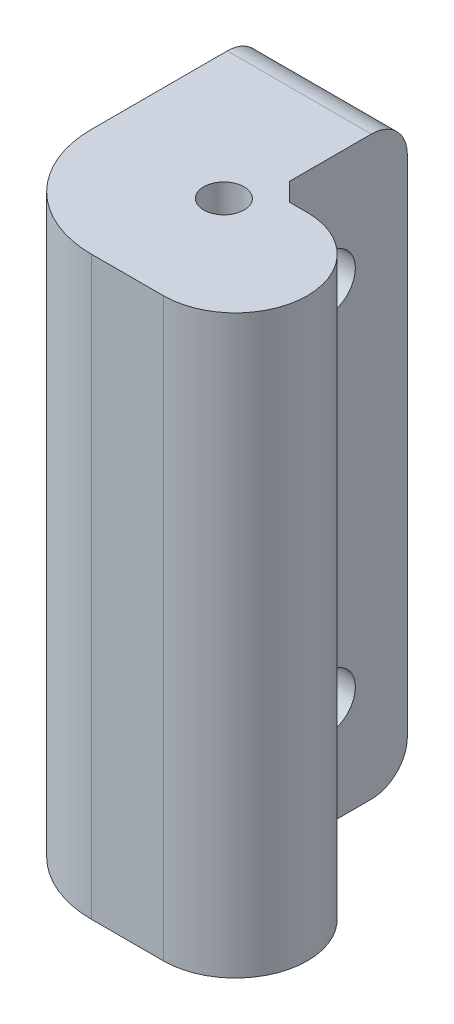
SolidWorks part; units mm, degrees
material "Polycarbonate"
ref_plane "Front Plane" through (0, 0, 0) normal (0, 0, 1) x (1, 0, 0)
ref_plane "Top Plane" through (0, 0, 0) normal (0, 1, 0) x (1, 0, 0)
ref_plane "Right Plane" through (0, 0, 0) normal (1, 0, 0) x (0, 0, -1)
sketch "Sketch1" plane through (0, 0, 0) normal (0, 1, 0) x (1, 0, 0)
  line L0 (0, 0) -> (0, 5.9944)
  line L1 (0, 5.9944) -> (-6.35, 5.9944)
  line L2 (-6.35, 5.9944) -> (-6.35, -6.35)
  line L3 (-6.35, -6.35) -> (4.7625, -6.35)
  line L4 (4.7625, -6.35) -> (4.7625, 0)
  line L5 (4.7625, 0) -> (0, 0)
  dimension "D1" = 5.9944
  dimension "D2" = 6.35
  dimension "D3" = 4.7625
  dimension "D4" = 6.35
extrude "Boss-Extrude1" add sketch "Sketch1" along normal blind 25.4
chamfer "Chamfer1" distance 0.7937 angle 45 1 edges at (0, 12.7, 0)
hole_wizard "M2 Clearance Hole1" positions "Sketch3" profile "Sketch4" hole size "M2" standard "ANSI Metric" end condition up to next
sketch "Sketch3" plane through (0, 0, 0) normal (1, 0, 0) x (0, 0, -1)
  line L0 (2.5, 20.6391) -> (2.5, 4.6391) construction
  line L1 (0.7937, 25.4) -> (5.9944, 25.4) construction
  line L2 (5.9944, 25.4) -> (5.9944, 0) construction
  point P0 (2.5, 20.6391)
  point P3 (2.5, 4.6391)
  point P22 (2.5, 20.6391)
  dimension "D1" = 16
  dimension "D2" = 4.7609
  dimension "D3" = 3.4944
sketch "Sketch4" plane through (0, 20.6391, -2.5) normal (0, 1, 0) x (0, 0, -1)
  line L0 (0, 0) -> (0, 6.35)
  line L1 (0, 6.35) -> (1.2, 6.35)
  line L2 (1.2, 6.35) -> (1.2, 0)
  line L5 (1.2, 0) -> (0, 0)
  line L11 (0, -6.35) -> (0, 107.95) construction
  dimension "Thru Hole Dia." = 2.4
  dimension "Thru Hole Depth" = 6.35
fillet "Fillet1" radius 4.7625 1 edges at (-6.35, 12.7, 6.35)
fillet "Fillet3" 2 edges at (4.7625, 12.7, 6.35) (4.7625, 12.7, 0) type full round first side face at (1.5875, 12.7, 6.35) second side face at (2.7781, 12.7, 0) middle face at (4.7625, 12.7, 3.175)
fillet "Fillet4" radius 1.5875 2 edges at (-3.175, 25.4, -5.9944) (-3.175, 0, -5.9944)
ref_plane "Plane1" through (4.7625, 0, 0) normal (1, 0, 0) x (0, 0, -1)
sketch "Sketch5" plane through (0, 0, 0) normal (0, -1, 0) x (-1, 0, 0)
  line L0 (0, 0.7937) -> (0, 4.4069) construction
  line L4 (-1.5875, 0) -> (-0.7937, 0) construction
  circle A0 centre (0.7937, -1.303) radius 0.7938 construction
  circle A1 centre (0.7937, -1.303) radius 0.889
  dimension "D2" = 1.303
  dimension "D1" = 1.5875
  dimension "D3" = 1.778
extrude "Cut-Extrude2" cut sketch "Sketch5" against normal through all
